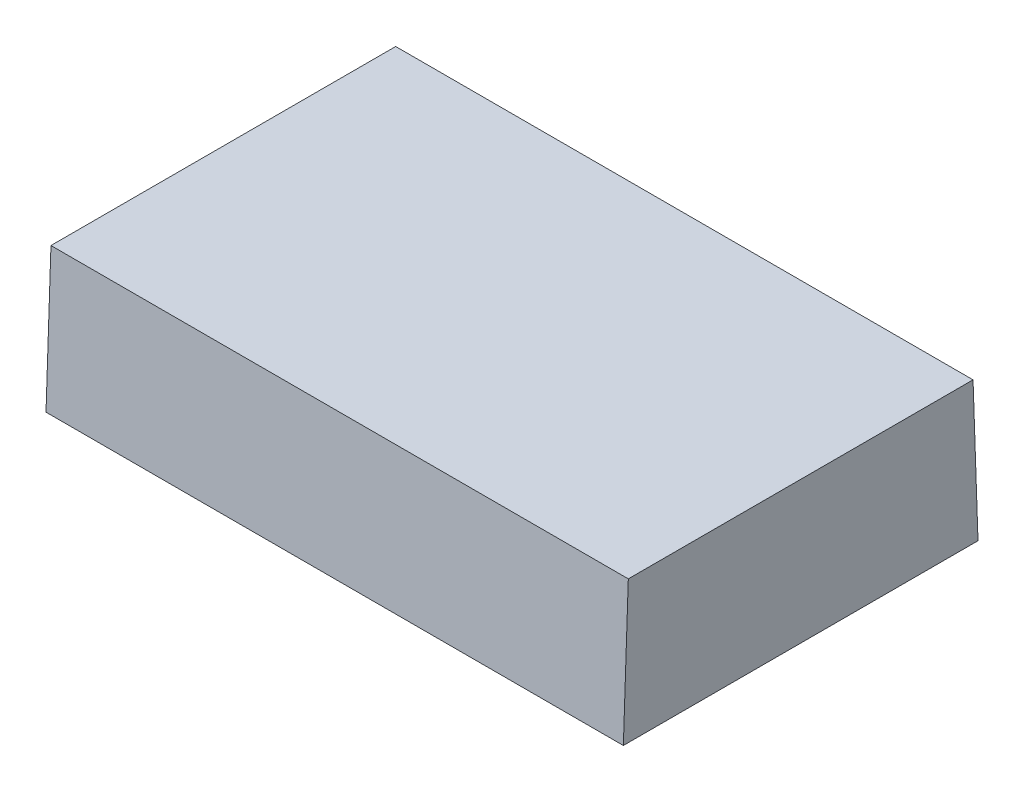
SolidWorks part; units mm, degrees
ref_plane "Front Plane" through (0, 0, 0) normal (0, 0, 1) x (1, 0, 0)
ref_plane "Top Plane" through (0, 0, 0) normal (0, 1, 0) x (1, 0, 0)
ref_plane "Right Plane" through (0, 0, 0) normal (1, 0, 0) x (0, 0, -1)
sketch "Sketch6" plane through (0, 0, 0) normal (1, 0, 0) x (0, 0, -1)
  line L0 (-63.5, -25.4) -> (63.5, -25.4)
  line L2 (63.5, -25.4) -> (61.726, 25.4)
  line L3 (61.726, 25.4) -> (-61.726, 25.4)
  line L4 (-61.726, 25.4) -> (-63.5, -25.4)
  line L5 (0, 0) -> (0, 57.1198) construction
  line L6 (0, 0) -> (71.7453, 0) construction
  dimension "D1" = 92
  dimension "D3" = 127
  dimension "D5" = 50.8
extrude "Boss-Extrude5" add sketch "Sketch6" along normal blind 206.756
shell "Shell2" thickness 6.35
